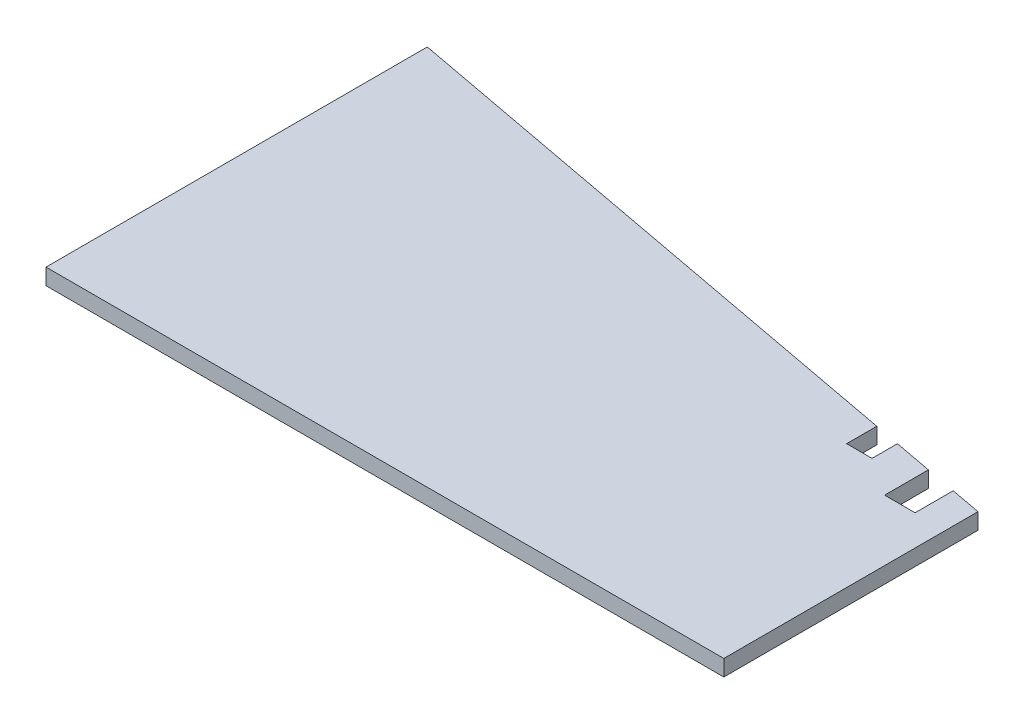
SolidWorks part; units mm, degrees
material "Balsa"
ref_plane "Front Plane" through (0, 0, 0) normal (0, 0, 1) x (1, 0, 0)
ref_plane "Top Plane" through (0, 0, 0) normal (0, 1, 0) x (1, 0, 0)
ref_plane "Right Plane" through (0, 0, 0) normal (1, 0, 0) x (0, 0, -1)
sketch "Sketch2" plane through (0, 0, 0) normal (0, 1, 0) x (1, 0, 0)
  line L0 (0, 0) -> (266.65, 0)
  line L1 (266.65, 0) -> (266.65, 100)
  line L2 (266.65, 100) -> (254.65, 102.2501)
  line L3 (0, 150) -> (0, 0)
  line L4 (242.65, 104.5003) -> (242.65, 87.2501)
  line L5 (242.65, 87.2501) -> (254.65, 87.2501)
  line L6 (254.65, 87.2501) -> (254.65, 102.2501)
  line L7 (242.65, 104.5003) -> (227.65, 107.313)
  line L8 (227.65, 97.313) -> (217.65, 97.313)
  line L9 (217.65, 97.313) -> (217.65, 109.1881)
  line L10 (227.65, 97.313) -> (227.65, 107.313)
  line L11 (217.65, 109.1881) -> (0, 150)
  point P10 (0, 0)
  point P12 (0, 0)
  point P14 (0, 0)
  dimension "D1" = 150
  dimension "D2" = 100
  dimension "D3" = 266.65
  dimension "D4" = 12
  dimension "D5" = 12
  dimension "D6" = 15
  dimension "D7" = 10
  dimension "D8" = 10
  dimension "D9" = 15
extrude "Boss-Extrude1" add sketch "Sketch2" along normal blind 6.35
